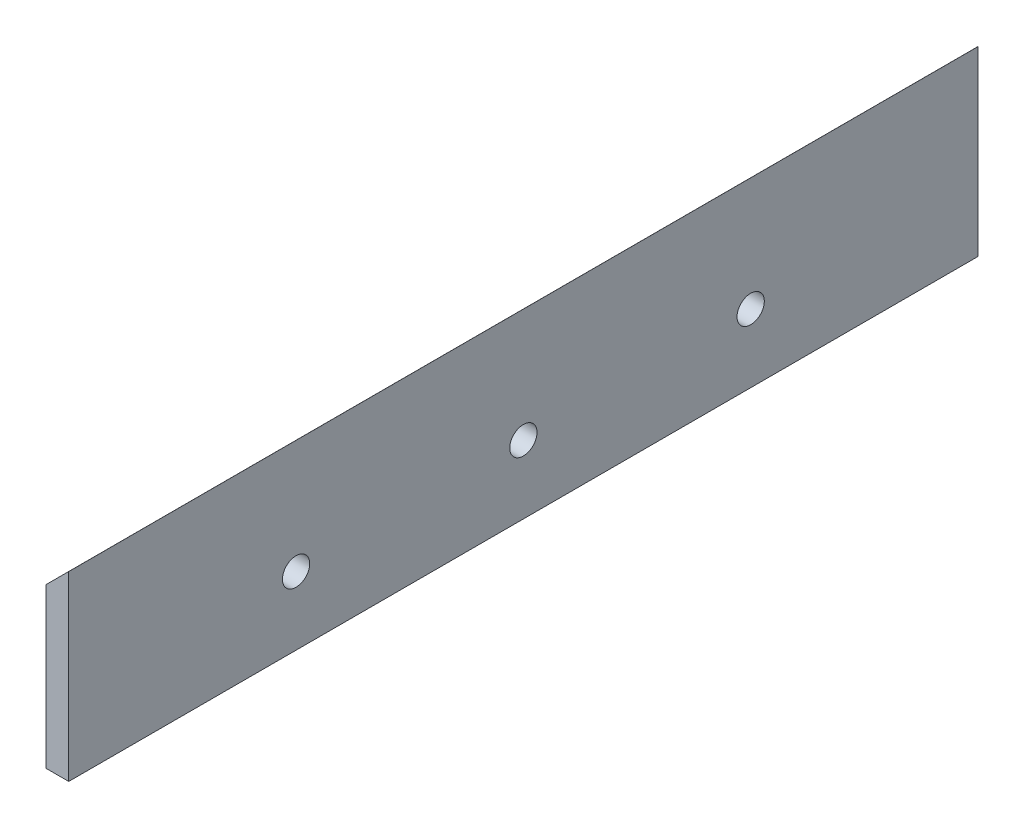
SolidWorks part; units mm, degrees
ref_plane "前基準面" through (0, 0, 0) normal (0, 0, 1) x (1, 0, 0)
ref_plane "上基準面" through (0, 0, 0) normal (0, 1, 0) x (1, 0, 0)
ref_plane "右基準面" through (0, 0, 0) normal (1, 0, 0) x (0, 0, -1)
sketch "草圖1" plane through (0, 0, 0) normal (0, 0, 1) x (1, 0, 0)
  line L0 (203.624, 1001.1769) -> (198.624, 1001.1769)
  line L1 (198.624, 1001.1769) -> (198.624, 1041.1769)
  line L7 (198.624, 1041.1769) -> (203.624, 1041.1629)
  line L8 (203.624, 1041.1629) -> (203.624, 1001.1769)
  dimension "D1" = 40
  dimension "D2" = 5
extrude "填料-伸長1" add sketch "草圖1" along normal blind 200
sketch "Sketch1" plane through (203.624, 0, 0) normal (1, 0, 0) x (0, 0, -1)
  line L0 (0, 1001.1769) -> (0, 1041.1629) construction
  line L1 (-200, 1001.1769) -> (0, 1001.1769) construction
  circle A0 centre (-50, 1016.1769) radius 3
  dimension "D1" = 6
  dimension "D2" = 50
  dimension "D3" = 15
chamfer "Chamfer1" distance 5 angle 45 1 edges at (198.624, 1041.1769, 100) first distance on face at (198.624, 1021.1769, 100)
extrude "Cut-Extrude1" cut sketch "Sketch1" against normal up to surface (5 mm away) up to face at (198.624, 1018.6769, 100)
pattern_linear "LPattern1" count 3 spacing 50 along (0, 0, 1) of "Cut-Extrude1"
